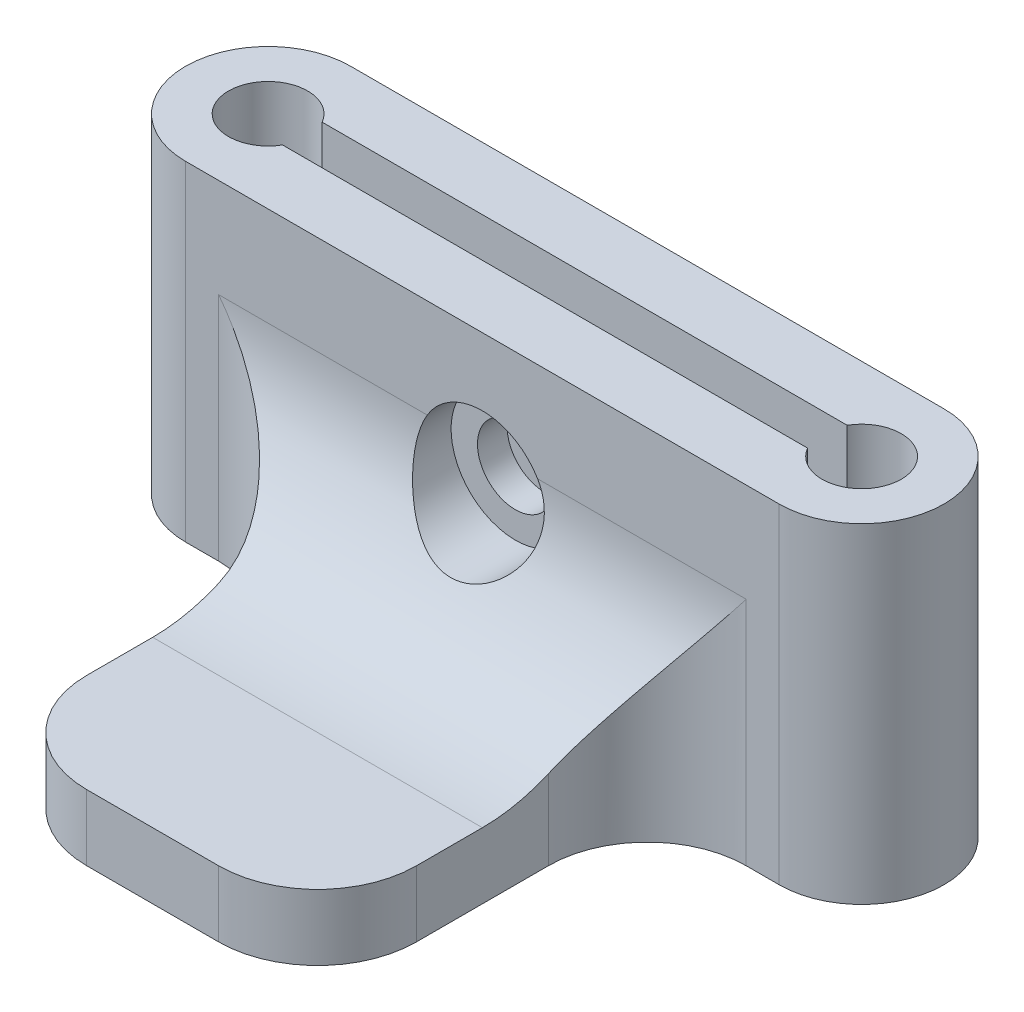
SolidWorks part; units mm, degrees
ref_plane "前视基准面" through (0, 0, 0) normal (0, 0, 1) x (1, 0, 0)
ref_plane "上视基准面" through (0, 0, 0) normal (0, 1, 0) x (1, 0, 0)
ref_plane "右视基准面" through (0, 0, 0) normal (1, 0, 0) x (0, 0, -1)
sketch "草图1" plane through (0, 0, 0) normal (0, 1, 0) x (1, 0, 0)
  line L0 (0, 0) -> (0, 4.7348) construction
  line L1 (0, 0) -> (9, 0) construction
  line L2 (-9, 0) -> (9, 0) construction
  line L3 (-6.4249, 17.0648) -> (6.4249, 17.0648) construction
  line L4 (-6.4249, 17.0648) -> (-6.4249, 3.25) construction
  line L5 (-6.4249, 3.25) -> (6.4249, 3.25) construction
  line L6 (6.4249, 17.0648) -> (6.4249, 3.25) construction
  line L7 (-6.4249, 17.0648) -> (6.4249, 3.25) construction
  line L8 (-6.4249, 3.25) -> (6.4249, 17.0648) construction
  line L9 (-9, 2.5) -> (9, 2.5)
  line L10 (-9, -2.5) -> (9, -2.5)
  circle A0 centre (0, 0) radius 11.5 construction
  circle A1 centre (9, 0) radius 1.2
  circle A2 centre (-9, 0) radius 1.2
  arc A3 (-9, 2.5) -> (-9, -2.5) centre (-9, 0) ccw
  arc A4 (9, -2.5) -> (9, 2.5) centre (9, 0) ccw
  point P8 (0, 10.1574)
  point P13 (0, 0)
  dimension "D1" = 23
  dimension "D3" = 2.4
  dimension "D2" = 18
  dimension "D4" = 3.25
extrude "凸台-拉伸1" add sketch "草图1" along normal blind 10
sketch "草图3" plane through (0, 0, 0) normal (0, -1, 0) x (1, 0, 0)
  line L0 (0, 0) -> (0, 5) construction
  line L1 (9, -2.5) -> (-9, -2.5) construction
  line L2 (-5, 12.5) -> (5, 12.5)
  line L3 (-5, 12.5) -> (-5, -2.5)
  line L4 (-5, -2.5) -> (5, -2.5)
  line L5 (5, 12.5) -> (5, -2.5)
  line L6 (-5, 12.5) -> (5, -2.5) construction
  line L7 (-5, -2.5) -> (5, 12.5) construction
  dimension "D1" = 10
  dimension "D2" = 15
extrude "凸台-拉伸2" add sketch "草图3" against normal blind 2
chamfer "倒角2" [suppressed] distance 10 angle 45
fillet "圆角2" radius 3 4 edges at (-5, 1, 12.5) (5, 1, 12.5) (5, 1, 2.5) (-5, 1, 2.5)
fillet "圆角3" radius 5 1 edges at (0, 2, 2.5)
sketch "草图4" plane through (0, 0, 0) normal (0, -1, 0) x (1, 0, 0)
  line L1 (-7.9608, -0.6) -> (7.9608, -0.6)
  line L2 (-7.9608, -0.6) -> (-7.9608, 0.6)
  line L3 (-7.9608, 0.6) -> (7.9608, 0.6)
  line L4 (7.9608, -0.6) -> (7.9608, 0.6)
  line L5 (-7.9608, -0.6) -> (7.9608, 0.6) construction
  line L6 (-7.9608, 0.6) -> (7.9608, -0.6) construction
  circle A0 centre (9, 0) radius 1.2 construction
  point P0 (0, 0)
  dimension "D1" = 1.2
extrude "切除-拉伸2" cut sketch "草图4" against normal through all
sketch "草图6" plane through (0, 0, 2.5) normal (0, 0, 1) x (1, 0, 0)
  line L0 (0, 0) -> (0, 6) construction
  line L1 (-9, 10) -> (9, 10) construction
  circle A0 centre (0, 6) radius 1.95
  dimension "D1" = 3.9
  dimension "D2" = 4
extrude "切除-拉伸4" cut sketch "草图6" against normal blind 1 and the other way through all
sketch "草图7" plane through (0, 0, 1.5) normal (0, 0, 1) x (1, 0, 0)
  circle A0 centre (0, 6) radius 1.15
  dimension "D1" = 2.3
extrude "切除-拉伸5" cut sketch "草图7" against normal through all
sketch "草图8" plane through (0, 0, -2.5) normal (0, 0, -1) x (-1, 0, 0)
  line L0 (0, 8.4249) -> (0, 6) construction
  line L1 (0, 8.4249) -> (-2.1, 7.2124)
  line L2 (-2.1, 7.2124) -> (-2.1, 4.7876)
  line L3 (-2.1, 4.7876) -> (0, 3.5751)
  line L4 (0, 3.5751) -> (2.1, 4.7876)
  line L5 (2.1, 4.7876) -> (2.1, 7.2124)
  line L6 (2.1, 7.2124) -> (0, 8.4249)
  circle A0 centre (0, 6) radius 1.15 construction
  circle A1 centre (0, 6) radius 1.15 construction
  circle A2 centre (0, 6) radius 2.1 construction
  dimension "D1" = 4.2
extrude "切除-拉伸6" cut sketch "草图8" against normal blind 1
